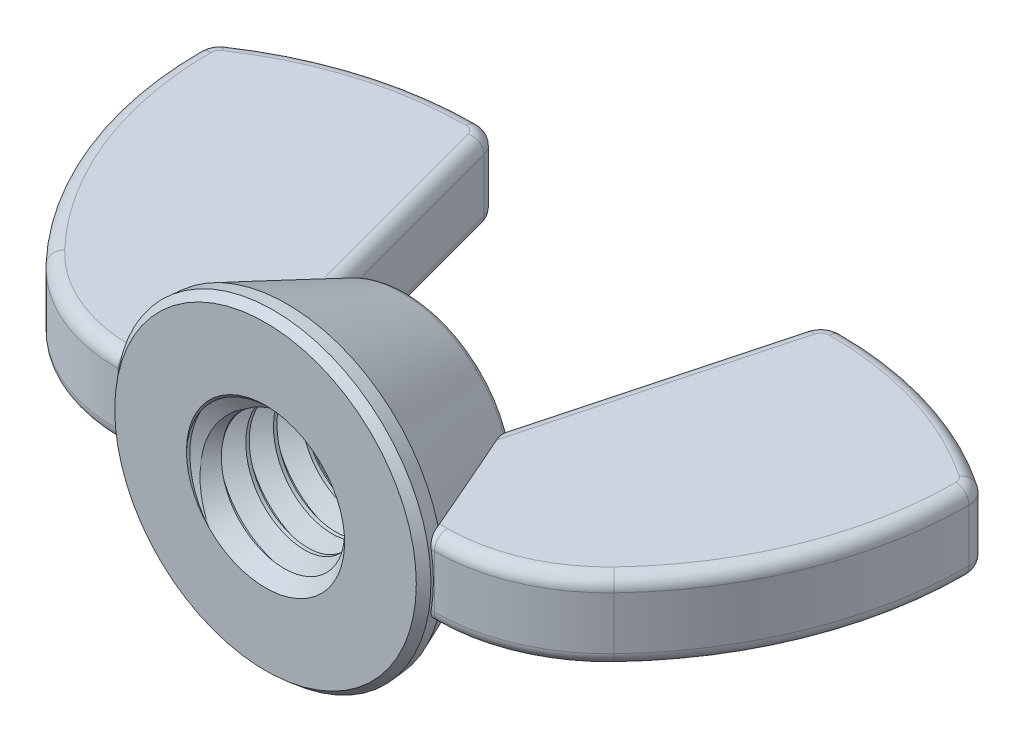
SolidWorks part; units mm, degrees
ref_plane "Front Plane" through (0, 0, 0) normal (0, 0, 1) x (1, 0, 0)
ref_plane "Top Plane" through (0, 0, 0) normal (0, 1, 0) x (1, 0, 0)
ref_plane "Right Plane" through (0, 0, 0) normal (1, 0, 0) x (0, 0, -1)
sketch "Sketch1" plane through (0, 0, 0) normal (0, 0, 1) x (1, 0, 0)
  circle A0 centre (0, 0) radius 2
  circle A1 centre (0, 0) radius 4
  dimension "D1" = 8
sketch "Sketch2" plane through (0, 0, 0) normal (0, 1, 0) x (1, 0, 0)
  line L0 (0, 0) -> (0, 10) construction
  line L1 (-2, 0) -> (2, 0) construction
  line L2 (-9.75, 10) -> (9.75, 10) construction
  line L3 (9.75, 10) -> (9.75, 0) construction
  line L4 (-9.75, 10) -> (-9.75, 0) construction
  line L5 (-9.75, 0) -> (9.75, 0) construction
  line L6 (-2.7274, 3.6) -> (2.7274, 3.6) construction
  line L7 (0, 0) -> (0, 3.6) construction
  line L8 (-4.3144, 0.54) -> (4, 0.54) construction
  line L9 (4, 0) -> (4, 3.6) construction
  line L10 (2.4547, 3.6) -> (4.2081, 10.1439)
  line L12 (2.7274, 3.6) -> (2.7274, 0.27) construction
  line L13 (-4, 0) -> (4, 0) construction
  line L14 (4, 0.54) -> (2.7274, 3.6) construction
  line L15 (4.2081, 10.1439) -> (10.0115, 8.3697)
  line L16 (10.0115, 8.3697) -> (5.5453, 0.27)
  line L17 (4, 0.27) -> (5.5453, 0.27)
  line L19 (2.4547, 0.27) -> (4, 0.27)
  line L20 (-2.4547, 3.6) -> (2.4547, 3.6) construction
  line L21 (2.4547, 3.6) -> (2.4547, 0.27)
  circle A3 centre (9.1944, 8.0385) radius 0.5556 construction
  circle A4 centre (4.5958, 9.4444) radius 0.5556 construction
  dimension "D6" = 1.1111
  dimension "D2" = 3.6
  dimension "D4" = 5.4548
  dimension "D1" = 0.54
  dimension "D3" = 22.582
  dimension "D5" = 0.27
  dimension "D8" = 17
  dimension "D9" = 4.9093
  dimension "D7" = 15
sketch "Sketch13" plane through (0, 0, 0) normal (0, 1, 0) x (1, 0, 0)
  line L1 (2.4547, 3.6) -> (2.4547, 0.27) construction
  line L2 (2.4547, 3.6) -> (4.2081, 10.1439) construction
  line L3 (-9.75, 10) -> (9.75, 10) construction
  line L4 (9.75, 10) -> (9.75, 0) construction
  line L5 (4, 0.27) -> (5.5453, 0.27) construction
  line L6 (2.4547, 0.27) -> (4, 0.27) construction
  line L7 (0, 0) -> (0, 3.6) construction
  line L8 (-2, 0) -> (2, 0) construction
  line L9 (0, 0) -> (0, 10) construction
  line L10 (-2.7274, 3.6) -> (2.7274, 3.6) construction
  line L11 (2.4547, 0.27) -> (4, 0.27)
  line L12 (2.4547, 3.6) -> (2.4547, 0.27)
  line L13 (2.4547, 3.6) -> (4.0592, 9.5882)
  circle A0 centre (9.1944, 8.0385) radius 0.5556 construction
  circle A1 centre (4.5958, 9.4444) radius 0.5556 construction
  arc A5 (9.75, 8.0385) -> (9.5051, 8.4991) centre (9.1944, 8.0385) ccw
  arc A6 (4.5958, 10) -> (4.0592, 9.5882) centre (4.5958, 9.4444) ccw
  arc A7 (7.1841, 1.6328) -> (9.75, 8.0385) centre (0.4711, 8.0385) ccw
  arc A8 (9.5051, 8.4991) -> (4.5958, 10) centre (4.5958, 1.2208) ccw
  arc A10 (4, 0.27) -> (7.1841, 1.6328) centre (4, 4.6712) ccw
extrude "Extrude2" add sketch "Sketch13" along normal mid plane 2
sketch "Sketch3" plane through (0, 0, 0) normal (0, 0, 1) x (1, 0, 0)
  circle A0 centre (0, 0) radius 4 construction
  circle A1 centre (0, 0) radius 4
extrude "Extrude1" add sketch "Sketch3" against normal up to vertex (0.54 mm away) draft 5 separate body up to point (4, 0, -0.54)
sketch "Sketch15" plane through (0, 0, -0.54) normal (0, 0, -1) x (-1, 0, 0)
  circle A1 centre (0, 0) radius 3.9528
  circle A2 centre (0, 0) radius 3.9528
  dimension "D1" = 0
extrude "Extrude3" add sketch "Sketch15" along normal up to vertex (3.06 mm away) draft 22.582 up to point (0, 0, -3.6)
fillet "Fillet3" radius 0.254 1 edges at (-2.6802, 0, -3.6)
sketch "Sketch12" plane through (0, 0, -3.6) normal (0, 0, -1) x (-1, 0, 0)
  circle A1 centre (0, 0) radius 3.9528
  circle A2 centre (0, 0) radius 3.9528 construction
  dimension "D1" = 7.9055
sketch "Sketch4" plane through (0, 0, 0) normal (0, 0, 1) x (1, 0, 0)
  circle A0 centre (0, 0) radius 2 construction
  circle A1 centre (0, 0) radius 2
extrude "Cut-Extrude1" cut sketch "Sketch4" against normal through all
sketch "Sketch5" plane through (0, 0, 0) normal (0, 0, 1) x (1, 0, 0)
  circle A0 centre (0, 0) radius 2 construction
  circle A1 centre (0, 0) radius 2
curve "Helix/Spiral1" pitch 0.7 height 5.6 radius 2 centre (0, 0, 0) axis (0, 0, -1) start towards (1, 0, 0) parameters "pitch"=0.7
sketch "Sketch6" plane through (0, 0, 0) normal (0, 1, 0) x (1, 0, 0)
  line L0 (-2, -0.6125) -> (-1.5453, -0.35)
  line L1 (-1.5453, -0.35) -> (-1.5453, -0.2625)
  line L2 (-1.5453, -0.2625) -> (-2, 0)
  line L3 (-2, -0.6125) -> (-2, 0)
  line L4 (-2, -0.3063) -> (-1.5453, -0.3063) construction
  line L5 (-1.7727, -0.4813) -> (-1.7727, -0.1313) construction
  line L6 (-2, 0) -> (2, 0) construction
  dimension "D1" = 60
  dimension "D2" = 0.0875
  dimension "D3" = 0.35
sweep "Sweep1" add profiles "Sketch6" path "Helix/Spiral1"
sketch "Sketch7" plane through (0, 0, 0) normal (0, 0, 1) x (1, 0, 0)
  circle A1 centre (0, 0) radius 4
  circle A2 centre (0, 0) radius 4
  dimension "D1" = 0
extrude "Cut-Extrude2" cut sketch "Sketch7" along normal through all
ref_plane "Plane1" through (0, 0, -3.6) normal (0, 0, 1) x (1, 0, 0)
sketch "Sketch8" plane through (0, 0, -3.6) normal (0, 0, 1) x (1, 0, 0)
  circle A0 centre (0, 0) radius 3.9528 construction
  circle A2 centre (0, 0) radius 3.9528
extrude "Cut-Extrude3" cut sketch "Sketch8" against normal through all
sketch "Sketch9" plane through (0, 0, 0) normal (0, 0, 1) x (1, 0, 0)
  circle A1 centre (0, 0) radius 2
  circle A2 centre (0, 0) radius 2
  dimension "D1" = 0
extrude "Cut-Extrude4" cut sketch "Sketch9" against normal through all draft 45
sketch "Sketch11" plane through (0, 0, -3.6) normal (0, 0, 1) x (1, 0, 0)
  circle A0 centre (0, 0) radius 2 construction
  circle A1 centre (0, 0) radius 1.9492
  circle A2 centre (0, 0) radius 2 construction
  dimension "D1" = 0.0508
extrude "Cut-Extrude5" cut sketch "Sketch11" along normal through all draft 45
chamfer "Chamfer1" distance 0.2025 angle 45 1 edges at (4, 0, 0) first distance on face at (-3.9528, 0, -0.54)
fillet "Fillet4" radius 0.3333 14 edges at (3.2273, 1, -0.27) (5.7318, 1, -0.625) (4.2576, 1, -9.8852) (7.1626, 1, -9.6164) (9.685, 1, -8.2993) (3.2273, -1, -0.27) (5.7318, -1, -0.625) (4.2576, -1, -9.8852) (7.1626, -1, -9.6164) (9.685, -1, -8.2993) (9.0847, 1, -4.5883) (9.0847, -1, -4.5883) (3.2569, 1, -6.5941) (3.2569, -1, -6.5941)
mirror "Mirror6" about plane through (0, 0, 0) normal (1, 0, 0) of bodies 108 113
combine bodies "Combine2" operation type add bodies to combine 116 108 107
equation "\"D1@Sketch1\" = \"thread dia@Sketch1\"*1.725"
equation "\"D2@Sketch2\" = \"B@Sketch2\"*.36"
equation "\"D3@Helix/Spiral1\" = \"D2@Sketch2\"+2"
equation "\"D2@Sketch6\" = \"pitch@Helix/Spiral1\"*.125"
equation "\"D3@Sketch6\" = \"pitch@Helix/Spiral1\"*.5"
equation "\"D4@Sketch2\" = \"D1@Sketch12\"*.69"
equation "\"D1@Extrude2\" = \"D1@Sketch1\"*.25"
equation "\"D1@Sketch2\" = \"D2@Sketch2\"*.150"
equation "\"D5@Sketch2\" = \"D1@Sketch2\"/2"
equation "\"D3@Extrude3\" = \"D3@Sketch2\""
equation "\"D1@Chamfer1\" = \"D5@Sketch2\"*.75"
equation "\"D9@Sketch2\" = \"D4@Sketch2\"*.9"
equation "\"D6@Sketch2\" = \"D1@Extrude2\"/1.8"
equation "\"D1@Fillet4\" = \"D1@Extrude2\"/6"
